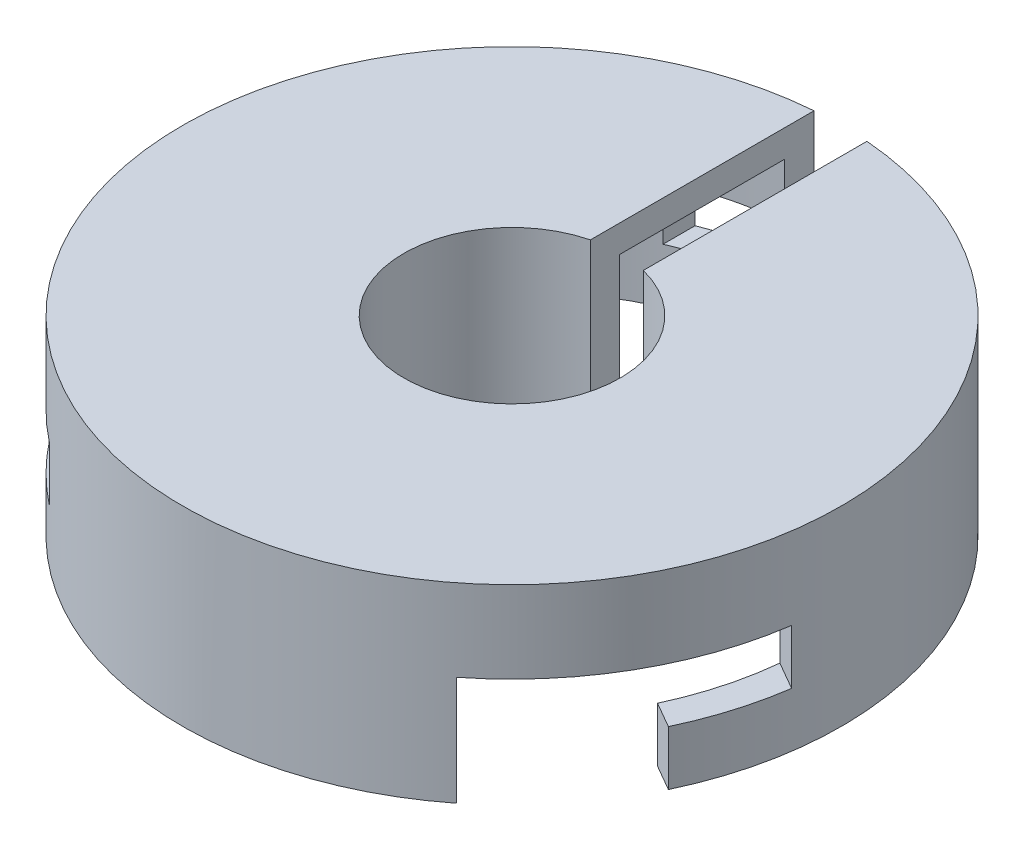
SolidWorks part; units mm, degrees
note: The reader was unsure of these and kept them because the rebuilt part matched: shared geometry of "Sketch1<6>", "Sketch1<7>", "Sketch1<8>", "Sketch1<9>".
ref_plane "Front Plane" through (0, 0, 0) normal (0, 0, 1) x (1, 0, 0)
ref_plane "Top Plane" through (0, 0, 0) normal (0, 1, 0) x (1, 0, 0)
ref_plane "Right Plane" through (0, 0, 0) normal (1, 0, 0) x (0, 0, -1)
sketch "Sketch1" plane through (0, 0, 0) normal (0, 1, 0) x (1, 0, 0)
  line L0 (0, 0) -> (0, 22) construction
  line L1 (17.4054, -4.8529) -> (10.9427, -1.1216)
  line L2 (12.9054, -12.6471) -> (6.4427, -8.9158)
  line L3 (-4.5, 17.5) -> (-4.5, 10.0374)
  line L4 (4.5, 17.5) -> (4.5, 10.0374)
  line L5 (-12.9054, -12.6471) -> (-6.4427, -8.9158)
  line L6 (-17.4054, -4.8529) -> (-10.9427, -1.1216)
  line L7 (-0.9701, 12.0433) -> (-0.9701, 3.8433)
  line L8 (0.9701, 12.0433) -> (0.9701, 3.8433)
  line L9 (10.9149, -5.1816) -> (3.8134, -1.0816)
  line L10 (-9.9448, -6.8618) -> (-2.8434, -2.7618)
  circle A0 centre (0, 0) radius 22
  circle A1 centre (0, 0) radius 11
  circle A2 centre (0, 0) radius 3.9639
  circle A3 centre (0, 0) radius 17.5 construction
  arc A4 (12.9054, -12.6471) -> (17.4054, -4.8529) centre (15.1554, -8.75) ccw
  circle A5 centre (15.1554, -8.75) radius 2.75 construction
  circle A6 centre (0, 17.5) radius 2.75 construction
  arc A7 (-17.4054, -4.8529) -> (-12.9054, -12.6471) centre (-15.1554, -8.75) ccw
  circle A8 centre (-15.1554, -8.75) radius 2.75 construction
  arc A9 (4.5, 17.5) -> (-4.5, 17.5) centre (0, 17.5) ccw
  circle A10 centre (0, 0) radius 12.0823
  circle A11 centre (-15.1554, -8.75) radius 2.75
  circle A12 centre (0, 17.5) radius 2.75
  circle A13 centre (15.1554, -8.75) radius 2.75
  circle A14 centre (0, 0) radius 5
  point P8 (0, 0)
  point P9 (0, 17.5)
  point P29 (0, 0)
  point P37 (0, 0)
  point P38 (0, 0)
  point P44 (0, 0)
  dimension "D1" = 3
  dimension "D2" = 3
extrude "Boss-Extrude3" add sketch "Sketch1" against normal blind 7 contours A14 A2 | L9 A14 L8 A2 | L7 A14 L10 A2
extrude "Boss-Extrude4" add sketch "Sketch1<6>" against normal blind 1 contours A14 L10 A1 L9 | A14 L7 A1 L10 | A14 L9 A1 L8 | A10
sketch "Sketch1<6>" plane through (0, 0, 0) normal (0, 1, 0) x (1, 0, 0) same geometry as "Sketch1"
extrude "Boss-Extrude5" add sketch "Sketch1<7>" against normal blind 7 contours L5 A10 L2 A1 | L1 A10 L4 A1 | L3 A10 L6 A1
sketch "Sketch1<7>" plane through (0, 0, 0) normal (0, 1, 0) x (1, 0, 0) same geometry as "Sketch1"
extrude "Boss-Extrude6" add sketch "Sketch1<8>" against normal blind 3 contours L6 A10 L5 A1 | L2 A10 L1 A1 | L7 A10 L3 A1 | L4 A10 L8 A1 | L10 A10 L5 A1 | L9 A10 L1 A1
sketch "Sketch1<8>" plane through (0, 0, 0) normal (0, 1, 0) x (1, 0, 0) same geometry as "Sketch1"
extrude "Boss-Extrude7" add sketch "Sketch1<9>" against normal blind 2 from offset 5 contours L10 A10 L5 A1 | L9 A10 L1 A1 | L7 A10 L3 A1
sketch "Sketch1<9>" plane through (0, 0, 0) normal (0, 1, 0) x (1, 0, 0) same geometry as "Sketch1"
